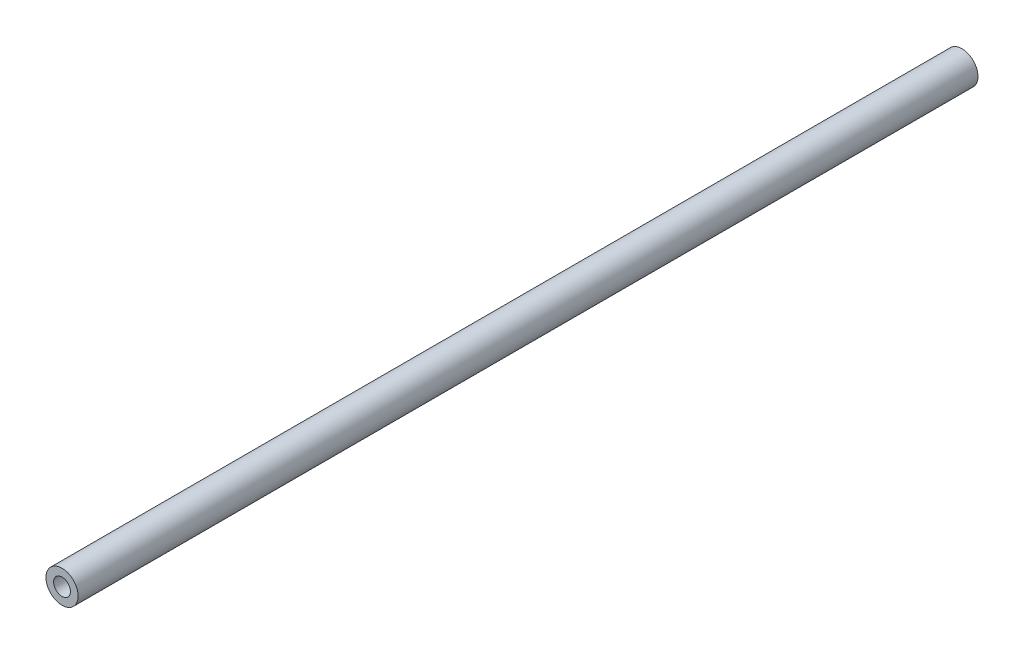
SolidWorks part; units mm, degrees
material "6061-T6 (SS)"
ref_plane "Front Plane" through (0, 0, 0) normal (0, 0, 1) x (1, 0, 0)
ref_plane "Top Plane" through (0, 0, 0) normal (0, 1, 0) x (1, 0, 0)
ref_plane "Right Plane" through (0, 0, 0) normal (1, 0, 0) x (0, 0, -1)
sketch "Sketch1" plane through (0, 0, 0) normal (0, 0, 1) x (1, 0, 0)
  circle A0 centre (0, 0) radius 2.4892
  circle A1 centre (0, 0) radius 4.7625
  dimension "D1" = 4.9784
  dimension "D2" = 9.525
extrude "Boss-Extrude1" add sketch "Sketch1" along normal mid plane 266.7
